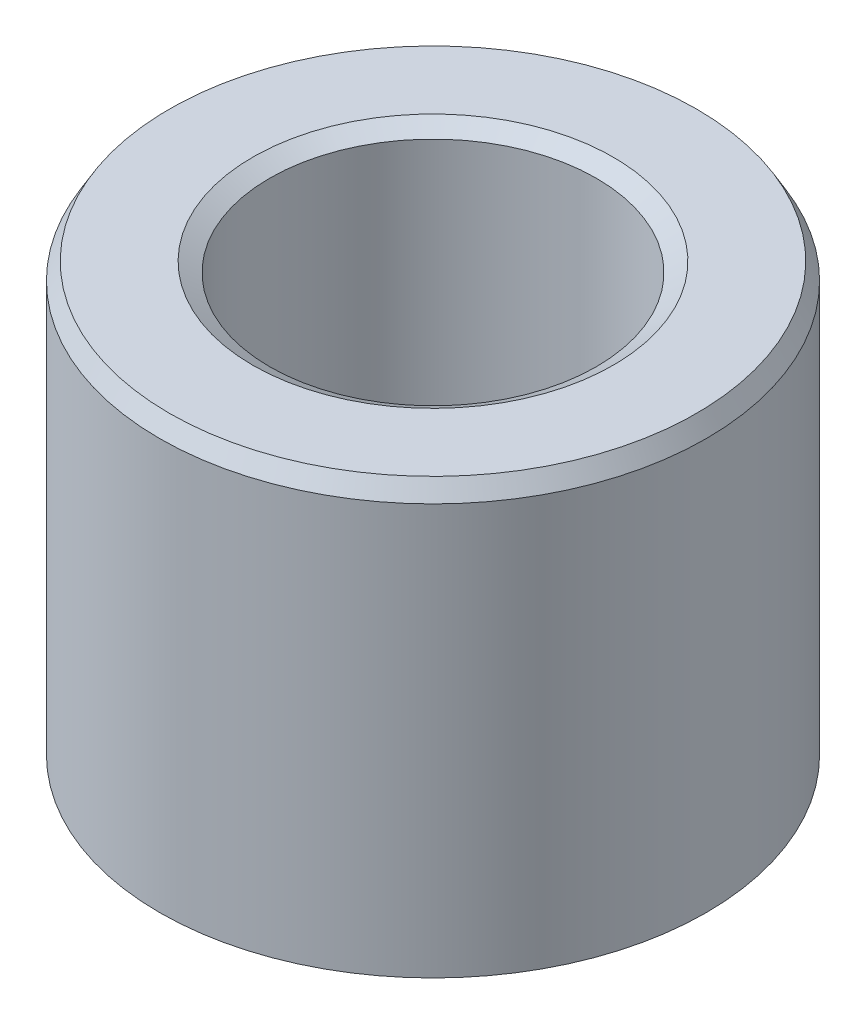
SolidWorks part; units mm, degrees
ref_plane "Front Plane" through (0, 0, 0) normal (0, 0, 1) x (1, 0, 0)
ref_plane "Top Plane" through (0, 0, 0) normal (0, 1, 0) x (1, 0, 0)
ref_plane "Right Plane" through (0, 0, 0) normal (1, 0, 0) x (0, 0, -1)
sketch "Sketch1" plane through (0, 0, 0) normal (0, 1, 0) x (1, 0, 0)
  circle A0 centre (0, 0) radius 32.5
  dimension "SLEEVE_OD" = 65
extrude "Boss-Extrude1" add sketch "Sketch1" along normal blind 51.9871
sketch "Sketch2" plane through (0, 0, 0) normal (0, 1, 0) x (1, 0, 0)
  circle A0 centre (0, 0) radius 19.4184
  dimension "BORE_D" = 38.8369
extrude "Cut-Extrude1" cut sketch "Sketch2" along normal through all
chamfer "Chamfer1" distance 2.0134 angle 30 4 edges at (0, 51.9871, 19.4184) (0, 0, 19.4184) (0, 0, 32.5) (0, 51.9871, 32.5) first distance on face at (0, 51.9871, 19.4184) first distance on face at (0, 0, 19.4184) first distance on face at (0, 51.9871, 32.5)
